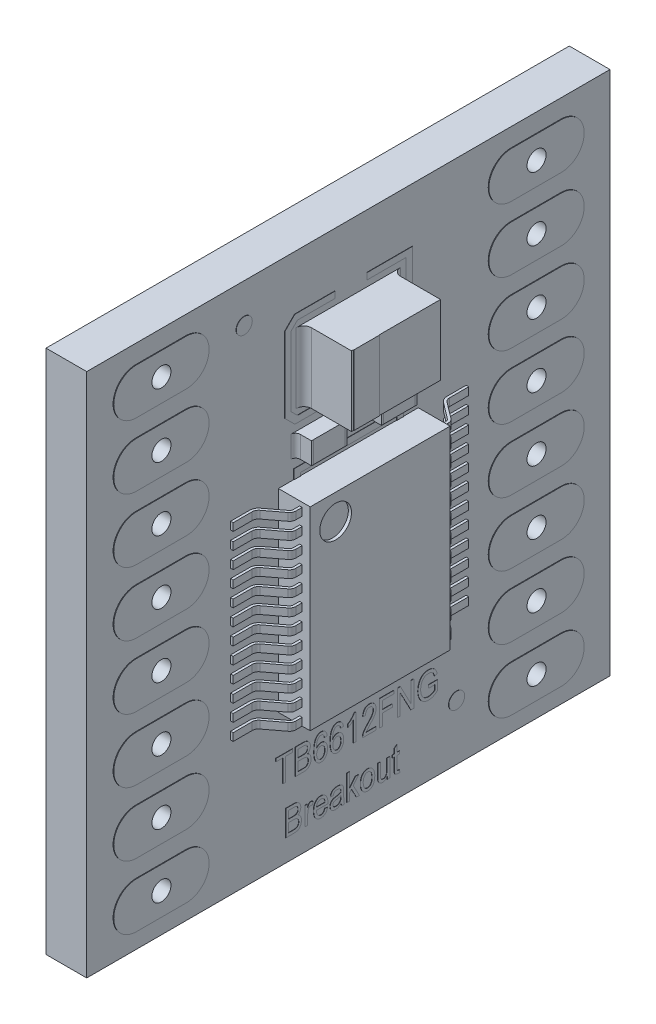
SolidWorks part; units mm, degrees
ref_plane "Front Plane" through (0, 0, 0) normal (0, 0, 1) x (1, 0, 0)
ref_plane "Top Plane" through (0, 0, 0) normal (0, 1, 0) x (1, 0, 0)
ref_plane "Right Plane" through (0, 0, 0) normal (1, 0, 0) x (0, 0, -1)
sketch "Sketch1" plane through (0, 0, 0) normal (1, 0, 0) x (0, 0, -1)
  line L1 (-10.4521, 10.4902) -> (10.4521, 10.4902)
  line L2 (-10.4521, 10.4902) -> (-10.4521, -10.4902)
  line L3 (-10.4521, -10.4902) -> (10.4521, -10.4902)
  line L4 (10.4521, 10.4902) -> (10.4521, -10.4902)
  line L5 (-10.4521, 10.4902) -> (10.4521, -10.4902) construction
  line L6 (-10.4521, -10.4902) -> (10.4521, 10.4902) construction
  point P0 (0, 0)
  dimension "D1" = 20.9804
  dimension "D2" = 20.9042
extrude "Boss-Extrude1" add sketch "Sketch1" along normal blind 1.6256
sketch "Sketch2" plane through (1.6256, 0, 0) normal (1, 0, 0) x (0, 0, -1)
  line L0 (-10.4521, -10.4902) -> (10.4521, -10.4902) construction
  line L1 (-2.794, 2.6162) -> (2.794, 2.6162)
  line L2 (-2.794, 2.6162) -> (-2.794, -5.1308)
  line L3 (-2.794, -5.1308) -> (2.794, -5.1308)
  line L4 (2.794, 2.6162) -> (2.794, -5.1308)
  line L5 (-2.794, 2.6162) -> (2.794, -5.1308) construction
  line L6 (-2.794, -5.1308) -> (2.794, 2.6162) construction
  point P0 (0, 0)
  dimension "D1" = 5.588
  dimension "D2" = 7.747
  dimension "D3" = 5.3594
extrude "Boss-Extrude2" add sketch "Sketch2" along normal blind 1.27
sketch "Sketch7" plane through (2.8956, 0, 0) normal (1, 0, 0) x (0, 0, -1)
  line L0 (-2.794, 2.6162) -> (-2.794, -5.1308) construction
  line L1 (2.794, 2.6162) -> (-2.794, 2.6162) construction
  circle A0 centre (-1.778, 1.6002) radius 0.635
  dimension "D1" = 1.27
  dimension "D2" = 1.016
  dimension "D3" = 1.016
extrude "Cut-Extrude2" cut sketch "Sketch7" against normal blind 0.127
sketch "Sketch4" plane through (1.6256, 0, 0) normal (1, 0, 0) x (0, 0, -1)
  line L0 (-7.493, 8.8392) -> (0, 8.8392) construction
  line L1 (0, 8.8392) -> (7.493, 8.8392) construction
  line L2 (0, 0) -> (0, 8.8392) construction
  line L3 (10.4521, 10.4902) -> (-10.4521, 10.4902) construction
  circle A0 centre (-7.493, 8.8392) radius 0.381
  circle A1 centre (7.493, 8.8392) radius 0.381
  dimension "D2" = 0.762
  dimension "D1" = 14.986
  dimension "D3" = 1.27
extrude "Cut-Extrude1" cut sketch "Sketch4" against normal through all
sketch "Sketch5" plane through (1.6256, 0, 0) normal (1, 0, 0) x (0, 0, -1)
  line L0 (-8.4836, 8.8392) -> (-6.5024, 8.8392) construction
  line L1 (-8.4836, 9.7536) -> (-6.5024, 9.7536)
  line L2 (-8.4836, 7.9248) -> (-6.5024, 7.9248)
  line L3 (6.5024, 8.8392) -> (8.4836, 8.8392) construction
  line L4 (6.5024, 9.7536) -> (8.4836, 9.7536)
  line L5 (6.5024, 7.9248) -> (8.4836, 7.9248)
  arc A0 (-8.4836, 9.7536) -> (-8.4836, 7.9248) centre (-8.4836, 8.8392) ccw
  arc A1 (-6.5024, 7.9248) -> (-6.5024, 9.7536) centre (-6.5024, 8.8392) ccw
  arc A2 (6.5024, 9.7536) -> (6.5024, 7.9248) centre (6.5024, 8.8392) ccw
  arc A3 (8.4836, 7.9248) -> (8.4836, 9.7536) centre (8.4836, 8.8392) ccw
  circle A6 centre (7.493, 8.8392) radius 0.381 construction
  circle A7 centre (-7.493, 8.8392) radius 0.381 construction
  circle A8 centre (7.493, 8.8392) radius 0.381
  circle A9 centre (-7.493, 8.8392) radius 0.381
  point P3 (-7.493, 8.8392)
  point P8 (7.493, 8.8392)
  point P18 (7.493, 8.8392)
  dimension "D2" = 3.81
  dimension "D1" = 1.8288
extrude "Boss-Extrude3" add sketch "Sketch5" along normal blind 0.0254
sketch "Sketch6" plane through (0, 0, 0) normal (-1, 0, 0) x (0, 0, 1)
  line L0 (-6.5024, 7.9248) -> (-8.4836, 7.9248) construction
  line L1 (-8.4836, 9.7536) -> (-6.5024, 9.7536) construction
  line L2 (8.4836, 7.9248) -> (6.5024, 7.9248) construction
  line L3 (6.5024, 9.7536) -> (8.4836, 9.7536) construction
  line L4 (-6.5024, 7.9248) -> (-8.4836, 7.9248)
  line L5 (-8.4836, 9.7536) -> (-6.5024, 9.7536)
  line L6 (8.4836, 7.9248) -> (6.5024, 7.9248)
  line L7 (6.5024, 9.7536) -> (8.4836, 9.7536)
  circle A0 centre (-7.493, 8.8392) radius 0.381 construction
  arc A1 (-6.5024, 7.9248) -> (-6.5024, 9.7536) centre (-6.5024, 8.8392) ccw construction
  arc A2 (-8.4836, 9.7536) -> (-8.4836, 7.9248) centre (-8.4836, 8.8392) ccw construction
  circle A3 centre (7.493, 8.8392) radius 0.381 construction
  arc A4 (6.5024, 9.7536) -> (6.5024, 7.9248) centre (6.5024, 8.8392) ccw construction
  arc A5 (8.4836, 7.9248) -> (8.4836, 9.7536) centre (8.4836, 8.8392) ccw construction
  circle A6 centre (-7.493, 8.8392) radius 0.381
  arc A7 (-6.5024, 7.9248) -> (-6.5024, 9.7536) centre (-6.5024, 8.8392) ccw
  arc A8 (-8.4836, 9.7536) -> (-8.4836, 7.9248) centre (-8.4836, 8.8392) ccw
  circle A9 centre (7.493, 8.8392) radius 0.381
  arc A10 (6.5024, 9.7536) -> (6.5024, 7.9248) centre (6.5024, 8.8392) ccw
  arc A11 (8.4836, 7.9248) -> (8.4836, 9.7536) centre (8.4836, 8.8392) ccw
extrude "Boss-Extrude4" add sketch "Sketch6" along normal blind 0.0254
pattern_linear "LPattern1" count 8 spacing 2.54 along (0, -1, 0) of "Cut-Extrude1", "Boss-Extrude3", "Boss-Extrude4"
sketch "Sketch11" plane through (1.6256, 0, 0) normal (1, 0, 0) x (0, 0, -1)
  circle A0 centre (-4.1683, 8.9453) radius 0.3175
  circle A1 centre (4.3185, -8.2635) radius 0.3175
  dimension "D1" = 0.635
extrude "Boss-Extrude8" add sketch "Sketch11" along normal blind 0.0127
sketch "Sketch9" plane through (1.6256, 0, 0) normal (1, 0, 0) x (0, 0, -1)
  line L0 (-1.397, 3.81) -> (0, 3.81) construction
  line L1 (-2.032, 4.2418) -> (-0.762, 4.2418)
  line L2 (-2.032, 4.2418) -> (-2.032, 3.3782)
  line L3 (-2.032, 3.3782) -> (-0.762, 3.3782)
  line L4 (-0.762, 4.2418) -> (-0.762, 3.3782)
  line L5 (-2.032, 4.2418) -> (-0.762, 3.3782) construction
  line L6 (-2.032, 3.3782) -> (-0.762, 4.2418) construction
  line L7 (0.762, 4.2418) -> (2.032, 4.2418)
  line L8 (0.762, 4.2418) -> (0.762, 3.3782)
  line L9 (0.762, 3.3782) -> (2.032, 3.3782)
  line L10 (2.032, 4.2418) -> (2.032, 3.3782)
  line L11 (0.762, 4.2418) -> (2.032, 3.3782) construction
  line L12 (0.762, 3.3782) -> (2.032, 4.2418) construction
  line L13 (0, 3.81) -> (1.397, 3.81) construction
  line L14 (0, 3.81) -> (0, 0) construction
  line L15 (2.794, 2.6162) -> (-2.794, 2.6162) construction
  point P0 (-1.397, 3.81)
  point P5 (1.397, 3.81)
  dimension "D1" = 0.8636
  dimension "D2" = 1.27
  dimension "D3" = 1.397
  dimension "D4" = 0.762
extrude "Boss-Extrude6" add sketch "Sketch9" along normal blind 0.635
sketch "Sketch10" plane through (1.6256, 0, 0) normal (1, 0, 0) x (0, 0, -1)
  line L1 (-0.762, 4.2418) -> (-0.6858, 4.2418)
  line L2 (-0.762, 4.2418) -> (-0.762, 3.3782)
  line L3 (-0.762, 3.3782) -> (-0.6858, 3.3782)
  line L4 (-0.6858, 4.2418) -> (-0.6858, 3.3782)
  line L5 (-2.032, 4.2418) -> (-2.1082, 4.2418)
  line L6 (-2.032, 4.2418) -> (-2.032, 3.3782)
  line L7 (-2.032, 3.3782) -> (-2.1082, 3.3782)
  line L8 (-2.1082, 4.2418) -> (-2.1082, 3.3782)
  line L9 (0.762, 4.2418) -> (0.6858, 4.2418)
  line L10 (0.762, 4.2418) -> (0.762, 3.3782)
  line L11 (0.762, 3.3782) -> (0.6858, 3.3782)
  line L12 (0.6858, 4.2418) -> (0.6858, 3.3782)
  line L13 (2.032, 4.2418) -> (2.1082, 4.2418)
  line L14 (2.032, 4.2418) -> (2.032, 3.3782)
  line L15 (2.032, 3.3782) -> (2.1082, 3.3782)
  line L16 (2.1082, 4.2418) -> (2.1082, 3.3782)
  line L17 (-2.032, 3.3782) -> (-0.762, 3.3782) construction
  dimension "D1" = 0.0762
extrude "Boss-Extrude7" add sketch "Sketch10" along normal blind 0.6363
fillet "Fillet1" radius 0.1905 4 edges at (1.6256, 3.81, -2.1082) (1.6256, 3.81, -0.6858) (1.6256, 3.81, 0.6858) (1.6256, 3.81, 2.1082)
sketch "Sketch12" plane through (1.6256, 0, 0) normal (1, 0, 0) x (0, 0, -1)
  line L0 (0, 0) -> (0, 6.4262) construction
  line L1 (-1.778, 5.0292) -> (1.778, 5.0292)
  line L2 (-1.778, 5.0292) -> (-1.778, 7.8232)
  line L3 (-1.778, 7.8232) -> (1.778, 7.8232)
  line L4 (1.778, 5.0292) -> (1.778, 7.8232)
  line L5 (-1.778, 5.0292) -> (1.778, 7.8232) construction
  line L6 (-1.778, 7.8232) -> (1.778, 5.0292) construction
  line L8 (10.4521, 10.4902) -> (-10.4521, 10.4902) construction
  point P0 (0, 6.4262)
  dimension "D1" = 2.794
  dimension "D2" = 3.556
  dimension "D3" = 2.667
extrude "Boss-Extrude9" add sketch "Sketch12" along normal blind 1.905
fillet "Fillet2" radius 0.3048 2 edges at (1.6256, 6.4262, -1.778) (1.6256, 6.4262, 1.778)
sketch "Sketch13" plane through (3.5306, 0, 0) normal (1, 0, 0) x (0, 0, -1)
  line L0 (1.778, 7.8232) -> (-1.778, 7.8232) construction
  line L1 (-1.6958, 7.8232) -> (-0.6798, 7.8232)
  line L2 (-1.6958, 7.8232) -> (-1.6958, 5.0292)
  line L3 (-1.6958, 5.0292) -> (-0.6798, 5.0292)
  line L4 (-0.6798, 7.8232) -> (-0.6798, 5.0292)
  line L5 (-2.0828, 5.0292) -> (2.0828, 5.0292) construction
  dimension "D1" = 1.016
extrude "Boss-Extrude10" add sketch "Sketch13" along normal blind 0.0127
sketch "Sketch14" plane through (0, -5.1308, 0) normal (0, -1, 0) x (1, 0, 0)
  line L0 (2.5745, -2.794) -> (2.5745, -3.048)
  line L1 (2.8956, -2.794) -> (1.6256, -2.794) construction
  line L2 (2.4739, -3.2504) -> (1.8278, -3.74)
  line L3 (1.7272, -3.9425) -> (1.7272, -4.7045)
  line L4 (2.4729, -2.794) -> (2.4729, -3.048)
  line L5 (2.4126, -3.1695) -> (1.7664, -3.659)
  line L6 (1.6256, -3.9425) -> (1.6256, -4.7045)
  line L7 (2.5745, -2.794) -> (2.4729, -2.794)
  line L8 (1.7272, -4.7045) -> (1.6256, -4.7045)
  line L9 (1.6256, 10.4521) -> (1.6256, -10.4521) construction
  line L10 (2.8956, 0) -> (-1.1531, 0) construction
  line L11 (2.8956, 2.794) -> (2.8956, -2.794) construction
  line L12 (2.5745, 2.794) -> (2.4729, 2.794)
  line L13 (2.5745, 2.794) -> (2.5745, 3.048)
  line L14 (2.4729, 2.794) -> (2.4729, 3.048)
  line L15 (2.4739, 3.2504) -> (1.8278, 3.74)
  line L16 (2.4126, 3.1695) -> (1.7664, 3.659)
  line L17 (1.7272, 3.9425) -> (1.7272, 4.7045)
  line L18 (1.7272, 4.7045) -> (1.6256, 4.7045)
  line L19 (1.6256, 3.9425) -> (1.6256, 4.7045)
  arc A0 (1.8278, -3.74) -> (1.7272, -3.9425) centre (1.9812, -3.9425) ccw
  arc A1 (2.5745, -3.048) -> (2.4739, -3.2504) centre (2.3205, -3.048) cw
  arc A2 (2.4729, -3.048) -> (2.4126, -3.1695) centre (2.3205, -3.048) cw
  arc A3 (1.7664, -3.659) -> (1.6256, -3.9425) centre (1.9812, -3.9425) ccw
  arc A4 (2.4729, 3.048) -> (2.4126, 3.1695) centre (2.3205, 3.048) ccw
  arc A5 (2.5745, 3.048) -> (2.4739, 3.2504) centre (2.3205, 3.048) ccw
  arc A6 (1.7664, 3.659) -> (1.6256, 3.9425) centre (1.9812, 3.9425) cw
  arc A7 (1.8278, 3.74) -> (1.7272, 3.9425) centre (1.9812, 3.9425) cw
  dimension "D1" = 0.254
  dimension "D3" = 232.848
  dimension "D4" = 0.254
  dimension "D5" = 0.762
  dimension "D2" = 0.1016
extrude "Boss-Extrude11" add sketch "Sketch14" against normal blind 0.3048
pattern_linear "LPattern2" count 12 spacing 0.6604 along (0, 1, 0) of "Boss-Extrude11"
sketch "Sketch8" plane through (1.6256, 0, 0) normal (1, 0, 0) x (0, 0, -1)
  line L0 (-2.1843, 2.9972) -> (2.1843, 2.9972)
  line L1 (-1.9303, 2.7432) -> (1.9303, 2.7432)
  line L2 (-1.9303, 2.7432) -> (-1.9303, -5.2578)
  line L3 (-1.9303, -5.2578) -> (1.9303, -5.2578)
  line L4 (1.9303, 2.7432) -> (1.9303, -5.2578)
  line L5 (-1.9303, 2.7432) -> (1.9303, -5.2578) construction
  line L6 (-1.9303, -5.2578) -> (1.9303, 2.7432) construction
  line L7 (2.1843, 2.9972) -> (2.1843, -5.5118)
  line L8 (-2.1843, -5.5118) -> (2.1843, -5.5118)
  line L9 (-2.1843, 2.9972) -> (-2.1843, -5.5118)
  line L10 (2.794, 2.6162) -> (-2.794, 2.6162) construction
  line L11 (-0.5427, 8.3278) -> (-0.5427, 8.0738)
  line L12 (-2.794, -5.1308) -> (2.794, -5.1308) construction
  line L13 (2.5533, 8.3278) -> (2.5533, 4.5246)
  line L14 (-2.0453, 8.0738) -> (-0.5427, 8.0738)
  line L15 (-2.2993, 7.8198) -> (-2.2993, 5.0326)
  line L16 (-2.0453, 4.7786) -> (-0.5427, 4.7786)
  line L17 (2.2993, 8.0738) -> (2.2993, 4.7786)
  line L18 (-2.2993, 8.0738) -> (-2.2993, 4.7786) construction
  line L19 (-2.2993, 7.8198) -> (-2.0453, 8.0738)
  line L20 (-2.1505, 4.5246) -> (-0.5427, 4.5246)
  line L21 (-2.5533, 7.925) -> (-2.1505, 8.3278)
  line L22 (-2.1505, 8.3278) -> (-0.5427, 8.3278)
  line L23 (0.7387, 8.3278) -> (0.7387, 8.0738)
  line L24 (0.7387, 8.3278) -> (2.5533, 8.3278)
  line L25 (-2.5533, 8.3278) -> (2.5533, 8.3278) construction
  line L26 (0.7387, 8.0738) -> (2.2993, 8.0738)
  line L27 (-2.2993, 8.0738) -> (2.2993, 8.0738) construction
  line L28 (-2.2993, 5.0326) -> (-2.0453, 4.7786)
  line L29 (-2.5533, 4.9274) -> (-2.1505, 4.5246)
  line L30 (0.7387, 4.7786) -> (2.2993, 4.7786)
  line L31 (-2.2993, 4.7786) -> (2.2993, 4.7786) construction
  line L32 (0.7387, 4.5246) -> (2.5533, 4.5246)
  line L33 (-2.5533, 4.5246) -> (2.5533, 4.5246) construction
  line L34 (0.7387, 4.7786) -> (0.7387, 4.5246)
  line L35 (-0.5427, 4.7786) -> (-0.5427, 4.5246)
  line L36 (-2.5533, 8.3278) -> (-2.5533, 4.5246) construction
  line L37 (-2.5533, 7.925) -> (-2.5533, 4.9274)
  line L38 (-2.4789, 7.9994) -> (-2.2249, 8.2534) construction
  line L39 (-2.4789, 4.853) -> (-2.2249, 4.599) construction
  line L40 (-2.5533, 7.8198) -> (-2.5533, 5.0326) construction
  text T0 "TB6612FNG\r\n Breakout" font "Arial Narrow" height 1.016
  point P1 (0, -1.2573)
  point P14 (0, 6.4262)
  dimension "D2" = 0.127
  dimension "D3" = 0.127
  dimension "D5" = 0.254
  dimension "D1" = 0.254
  dimension "D4" = 0.254
  dimension "D6" = 0.254
  dimension "D7" = 0.254
extrude "Boss-Extrude5" add sketch "Sketch8" along normal blind 0.0127
sketch "Sketch15" plane through (0, 0, 0) normal (-1, 0, 0) x (0, 0, 1)
  line L0 (5.2079, 12.1114) -> (5.2079, -12.5412) construction
  text T0 "PWMA" font "Century Gothic" height 1.016
  text T1 "AIN2" font "Century Gothic" height 1.016
  text T2 "AIN1" font "Century Gothic" height 1.016
  text T3 "STBY" font "Century Gothic" height 1.016
  text T4 "BIN1" font "Century Gothic" height 1.016
  text T5 "BIN2" font "Century Gothic" height 1.016
  text T6 "PWMB" font "Century Gothic" height 1.016
  text T7 "GND" font "Century Gothic" height 1.016
  text T8 "VM" font "Century Gothic" height 1.016
  text T9 "VCC" font "Century Gothic" height 1.016
  text T10 "GND" font "Century Gothic" height 1.016
  text T11 "A01" font "Century Gothic" height 1.016
  text T12 "A02" font "Century Gothic" height 1.016
  text T13 "B02" font "Century Gothic" height 1.016
  text T14 "B01" font "Century Gothic" height 1.016
  text T15 "GND" font "Century Gothic" height 1.016
extrude "Boss-Extrude12" add sketch "Sketch15" along normal blind 0.0254
